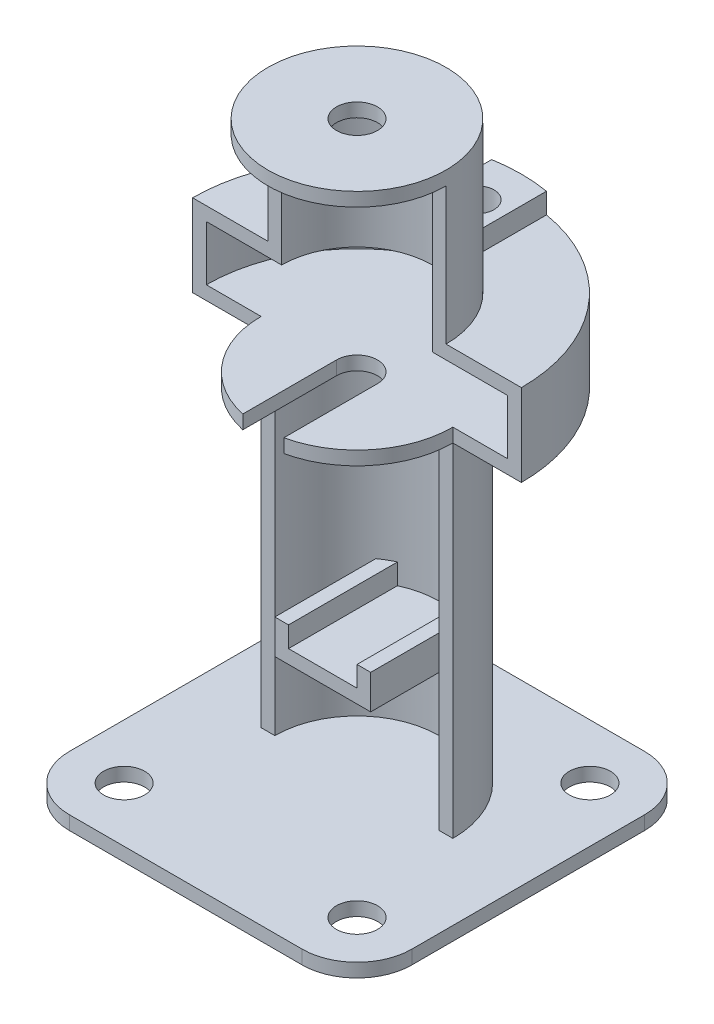
SolidWorks part; units mm, degrees
ref_plane "Front Plane" through (0, 0, 0) normal (0, 0, 1) x (1, 0, 0)
ref_plane "Top Plane" through (0, 0, 0) normal (0, 1, 0) x (1, 0, 0)
ref_plane "Right Plane" through (0, 0, 0) normal (1, 0, 0) x (0, 0, -1)
sketch "Sketch1" plane through (0, 0, 0) normal (0, 1, 0) x (1, 0, 0)
  line L0 (3, 0) -> (3, -13.6748)
  line L1 (-3, 0) -> (-3, -13.6748)
  line L2 (-14, 0) -> (-24, 0)
  line L3 (14, 0) -> (24, 0)
  circle A0 centre (0, 0) radius 14
  circle A1 centre (0, 0) radius 3
  arc A2 (24, 0) -> (-24, 0) centre (0, 0) ccw
  arc A3 (14, 0) -> (-14, 0) centre (0, 0) ccw
  dimension "D1" = 28
  dimension "D2" = 6
  dimension "D3" = 10
extrude "Motor-frontplate" add sketch "Sketch1" along normal blind 2 contours A1 L0 A0 L1 | L3 A2 L2 A3 region at (0, 0, -3.3937)
sketch "Sketch2" plane through (0, 0, 0) normal (0, -1, 0) x (1, 0, 0)
  line L2 (-12, 0) -> (-14, 0)
  line L3 (12, 0) -> (14, 0)
  arc A1 (-14, 0) -> (14, 0) centre (0, 0) ccw
  arc A3 (14, 0) -> (3, 13.6748) centre (0, 0) ccw construction
  arc A4 (-12, 0) -> (12, 0) centre (0, 0) ccw
  dimension "D1" = 2
extrude "Motorkrybbe" add sketch "Sketch2" along normal blind 50 contours A4 L3 A1 L2
sketch "Sketch5" plane through (0, 2, 0) normal (0, 1, 0) x (1, 0, 0)
  line L0 (-24, 0) -> (-22, 0)
  line L1 (24, 0) -> (22, 0)
  arc A1 (24, 0) -> (-24, 0) centre (0, 0) ccw construction
  arc A2 (22, 0) -> (-22, 0) centre (0, 0) ccw
  arc A3 (22, 0) -> (-22, 0) centre (0, 0) ccw
  arc A4 (24, 0) -> (-24, 0) centre (0, 0) ccw
  dimension "D1" = 2
extrude "Skygge - Kappe" add sketch "Sketch5" along normal blind 8 contours A3 L0 A4 L1
sketch "Sketch6" plane through (0, 10, 0) normal (0, 1, 0) x (1, 0, 0)
  line L0 (-24, 0) -> (-11, 0)
  line L1 (11, 0) -> (24, 0)
  arc A0 (-11, 0) -> (11, 0) centre (0, 0) cw
  arc A1 (24, 0) -> (-24, 0) centre (0, 0) ccw construction
  arc A2 (24, 0) -> (-24, 0) centre (0, 0) ccw
  dimension "D1" = 11
extrude "Skygge - Topp" add sketch "Sketch6" along normal blind 2
sketch "Sketch7" plane through (0, 12, 0) normal (0, 1, 0) x (1, 0, 0)
  line L0 (-4, 12.3693) -> (-4, 23.6643)
  line L1 (4, 23.6643) -> (4, 12.3693)
  arc A0 (24, 0) -> (-24, 0) centre (0, 0) ccw construction
  arc A1 (11, 0) -> (-11, 0) centre (0, 0) ccw construction
  arc A2 (24, 0) -> (-24, 0) centre (0, 0) ccw
  arc A3 (11, 0) -> (-11, 0) centre (0, 0) ccw
  arc A4 (4, 12.3693) -> (-4, 12.3693) centre (0, 0) ccw
  arc A5 (4, 23.6643) -> (-4, 23.6643) centre (0, 0) ccw
  point P6 (4, 12.3392)
  dimension "D3" = 2
  dimension "D1" = 4
  dimension "D2" = 4
extrude "LEDholder - Topp" add sketch "Sketch7" along normal blind 3 contours L1 A4 L0 A5
sketch "Sketch8" plane through (0, 0, 0) normal (0, -1, 0) x (1, 0, 0)
  line L0 (4, -23.6643) -> (4, -13.4164)
  line L1 (4, -23.6643) -> (4, -12.3693) construction
  line L2 (-4, -23.6643) -> (-4, -13.4164)
  line L3 (-4, -12.3693) -> (-4, -23.6643) construction
  arc A0 (-14, 0) -> (14, 0) centre (0, 0) ccw construction
  arc A1 (4, -13.4164) -> (-4.105, -13.3846) centre (0, 0) cw
  arc A2 (4, -23.6643) -> (-4, -23.6643) centre (0, 0) cw
  point P16 (0, 0)
  arc M1 (14, 0) -> (-14, 0) centre (0, 0) cw
  arc M3 (-24, 0) -> (24, 0) centre (0, 0) ccw
extrude "LEDholder - Bunn" add sketch "Sketch8" along normal blind 3 contours L2 L0 M3 M1 region at (0, 0, -18.8468)
sketch "Sketch10" plane through (0, -3, 0) normal (0, -1, 0) x (1, 0, 0)
  line L2 (0, 0) -> (0, -14)
  line L3 (0, -14) -> (0, -15)
  line L4 (0, -15) -> (0, -17.5)
  arc A0 (-4, -13.4164) -> (4, -13.4164) centre (0, 0) ccw construction
  arc A1 (-4, -13.4164) -> (4, -13.4164) centre (0, 0) ccw
  circle A3 centre (0, -17.5) radius 2.5
  dimension "D1" = 5
  dimension "D2" = 1
extrude "LEDhull" cut sketch "Sketch10" against normal through all contours A3 region at (-1.7178, -3, -19.2178)
sketch "Sketch11" plane through (0, 12, 0) normal (0, 1, 0) x (1, 0, 0)
  line L0 (-24, 0) -> (-11, 0) construction
  line L1 (11, 0) -> (24, 0) construction
  line L2 (-13, 0) -> (-11, 0)
  line L3 (13, 0) -> (11, 0)
  arc A0 (-11, 0) -> (11, 0) centre (0, 0) cw
  arc A1 (11, 0) -> (-11, 0) centre (0, 0) ccw construction
  arc A2 (-13, 0) -> (13, 0) centre (0, 0) cw
  dimension "D1" = 2
extrude "Rotorkappe - Vegg" add sketch "Sketch11" along normal blind 20
sketch "Sketch12" plane through (0, 32, 0) normal (0, 1, 0) x (1, 0, 0)
  circle A0 centre (0, 0) radius 13
extrude "Boss-Extrude9" add sketch "Sketch12" along normal blind 2
hole_wizard "Laser - hull" positions "Sketch13" profile "Sketch15" hole size "Ø6.0" standard "ISO" end condition up to next
sketch "Sketch13" plane through (0, 34, 0) normal (0, 1, 0) x (1, 0, 0)
  point P0 (0, 0)
sketch "Sketch15" plane through (0, 34, 0) normal (1, 0, 0) x (0, 0, 1)
  line L0 (0, 0) -> (0, 2)
  line L1 (0, 2) -> (3, 2)
  line L2 (3, 2) -> (3, 0)
  line L5 (3, 0) -> (0, 0)
  line L11 (0, -6.35) -> (0, 107.95) construction
  dimension "Thru Hole Dia." = 6
  dimension "Thru Hole Depth" = 2
sketch "Sketch16" plane through (0, -50, 0) normal (0, -1, 0) x (1, 0, 0)
  line L1 (-17, -25) -> (17, -25)
  line L2 (-25, -17) -> (-25, 17)
  line L3 (-17, 25) -> (17, 25)
  line L4 (25, -17) -> (25, 17)
  line L5 (-25, -25) -> (25, 25) construction
  line L6 (-25, 25) -> (25, -25) construction
  arc A0 (-25, 17) -> (-17, 25) centre (-17, 17) cw
  arc A1 (-17, -25) -> (-25, -17) centre (-17, -17) cw
  arc A2 (17, -25) -> (25, -17) centre (17, -17) ccw
  arc A3 (17, 25) -> (25, 17) centre (17, 17) cw
  point P0 (0, 0)
  dimension "D3" = 8
  dimension "D1" = 50
  dimension "D2" = 50
extrude "Bunnplate" add sketch "Sketch16" along normal blind 2
hole_wizard "Ø6.0 (6) Diameter Hole2" positions "Sketch17" profile "Sketch18" hole size "Ø6.0" standard "ISO" end condition up to next
sketch "Sketch17" plane through (0, -50, 0) normal (0, 1, 0) x (1, 0, 0)
  point P0 (17, -17)
  point P3 (0, 0)
  point P4 (0, 0)
  dimension "D1" = 8
  dimension "D2" = 8
sketch "Sketch18" plane through (17, -50, 17) normal (1, 0, 0) x (0, 0, 1)
  line L0 (0, 0) -> (0, 2.001)
  line L1 (0, 2.001) -> (3, 2.001)
  line L2 (3, 2.001) -> (3, 0)
  line L5 (3, 0) -> (0, 0)
  line L11 (0, -6.35) -> (0, 107.95) construction
  dimension "Thru Hole Dia." = 6
  dimension "Thru Hole Depth" = 2.001
pattern_circular "CirPattern1" count 4 every 90 about axis through (0, -50, 0) along (0, -1, 0) of "Ø6.0 (6) Diameter Hole2"
sketch "Sketch19" plane through (0, 0, 0) normal (0, 0, 1) x (1, 0, 0)
  line L0 (0, -33) -> (-5, -33)
  line L9 (-5, -33) -> (-5, -30)
  line L10 (-5, -30) -> (-7, -30)
  line L11 (-7, -30) -> (-7, -35)
  line L12 (-7, -35) -> (0, -35)
  line L13 (0, -35) -> (0, -33)
  line L14 (0, 0) -> (0, -33) construction
  dimension "D1" = 30
  dimension "D2" = 2
  dimension "D3" = 3
  dimension "D4" = 2
  dimension "D5" = 5
extrude "Boss-Extrude12" add sketch "Sketch19" along normal blind 5 and the other way up to next
mirror "Mirror2" about plane through (0, -35, -25.002) normal (1, 0, 0) of "Boss-Extrude12"
